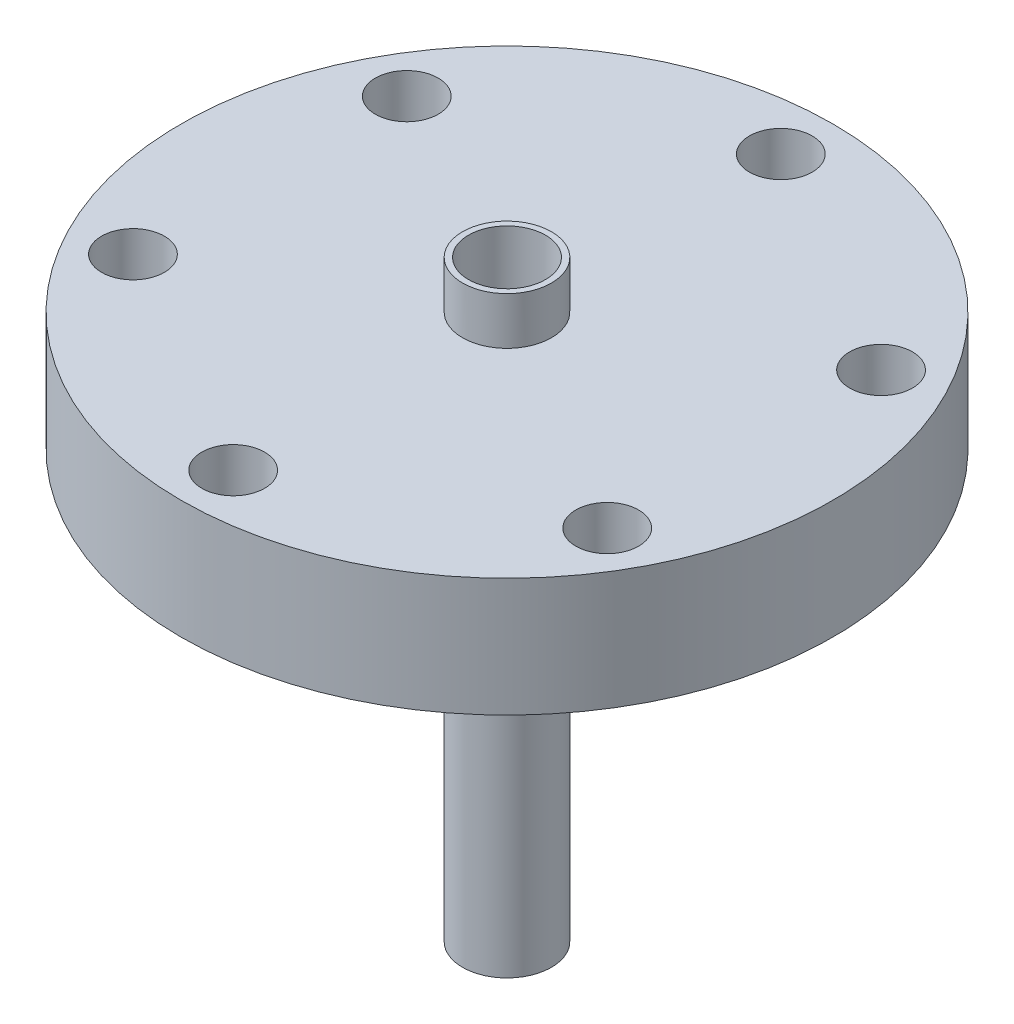
SolidWorks part; units mm, degrees
ref_plane "Front Plane" through (0, 0, 0) normal (0, 0, 1) x (1, 0, 0)
ref_plane "Top Plane" through (0, 0, 0) normal (0, 1, 0) x (1, 0, 0)
ref_plane "Right Plane" through (0, 0, 0) normal (1, 0, 0) x (0, 0, -1)
sketch "Sketch1" plane through (0, 0, 0) normal (0, 1, 0) x (1, 0, 0)
  circle A0 centre (0, 0) radius 34.925
  dimension "D1" = 69.85
extrude "Extrude1" add sketch "Sketch1" along normal blind 12.7
sketch "Sketch2" plane through (0, 0, 0) normal (0, 1, 0) x (1, 0, 0)
  circle A0 centre (0, 0) radius 4.7625
  dimension "D1" = 9.525
extrude "Cut-Extrude1" cut sketch "Sketch2" along normal through all
sketch "Sketch3" plane through (0, 0, 0) normal (0, 1, 0) x (1, 0, 0)
  circle A0 centre (0, 29.337) radius 3.3655
  dimension "D1" = 6.731
  dimension "D2" = 29.337
extrude "Cut-Extrude2" cut sketch "Sketch3" along normal through all
ref_axis "Axis1" through (0, 35.8582, 0) along (0, -1, 0)
pattern_circular "CirPattern1" count 6 over 360 about axis through (0, 35.8582, 0) along (0, -1, 0) of "Cut-Extrude2"
sketch "Sketch4" plane through (0, 0, 0) normal (0, 1, 0) x (1, 0, 0)
  line L0 (0, 0) -> (0, 16.8619)
ref_plane "Plane1" through (0, 0, 0) normal (0, -1, 0) x (1, 0, 0)
sketch "Sketch5" plane through (0, 0, 0) normal (0, -1, 0) x (1, 0, 0)
  circle A0 centre (0, 0) radius 4.7625
  dimension "D1" = 9.525
extrude "Extrude-Thin1" add sketch "Sketch5" along normal blind 45.72 and the other way blind 17.78 thin thin type one direction reverse wall 0.635
